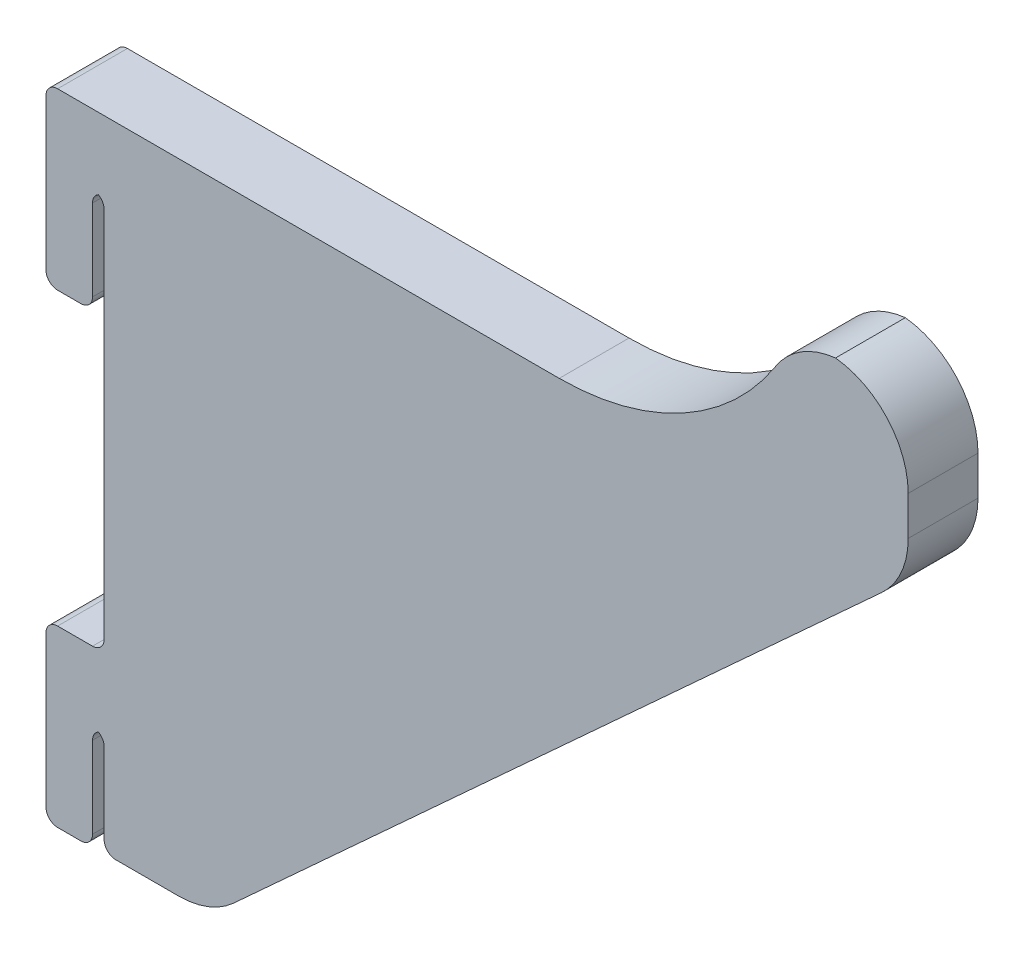
SolidWorks part; units mm, degrees
ref_plane "Plan de face" through (0, 0, 0) normal (0, 0, 1) x (1, 0, 0)
ref_plane "Plan de dessus" through (0, 0, 0) normal (0, 1, 0) x (1, 0, 0)
ref_plane "Plan de droite" through (0, 0, 0) normal (1, 0, 0) x (0, 0, -1)
sketch "Esquisse1" plane through (0, 0, 0) normal (0, 0, 1) x (1, 0, 0)
  line L0 (0, 0) -> (0, 9)
  line L1 (0, 9) -> (1, 9)
  line L4 (1, 0.0964) -> (10.1219, 0.0964)
  line L8 (10.1219, 55) -> (-4, 55)
  line L9 (1, 49) -> (0, 49)
  line L10 (0, 0) -> (-4, 0)
  line L11 (-4, 0) -> (-4, 15)
  line L12 (-4, 15) -> (1, 15)
  line L13 (1, 15) -> (1, 49)
  line L14 (0, 49) -> (0, 40)
  line L15 (0, 40) -> (-4, 40)
  line L16 (-4, 40) -> (-4, 55)
  line L17 (1, 9) -> (1, 0.0964)
  line L18 (10.1219, 55) -> (70.1219, 55) construction
  line L19 (10.1219, 55) -> (19.2932, 55)
  line L21 (60.4324, 68.4362) -> (70.1219, 68.4362)
  line L22 (70.1219, 68.4362) -> (70.1219, 55)
  line L23 (70.1219, 55) -> (10.1219, 0.0964)
  line L25 (40.1219, 55) -> (19.2932, 55)
  arc A1 (40.1219, 55) -> (60.4324, 68.4362) centre (40.1219, 77.0691) ccw
  point P11 (0.5, 9)
  dimension "D1" = 40
  dimension "D2" = 1
  dimension "D3" = 1
  dimension "D4" = 15
  dimension "D5" = 15
  dimension "D6" = 4
  dimension "D7" = 4
  dimension "D8" = 6
  dimension "D9" = 6
  dimension "D10" = 60
extrude "Boss.-Extru.1" add sketch "Esquisse1" along normal mid plane 6
fillet "Congé3" radius 1 12 edges at (1, 0.0964, 0) (1, 9, 0) (0, 9, 0) (0, 0, 0) (-4, 0, 0) (-4, 15, 0) (1, 15, 0) (0, 40, 0) (-4, 40, 0) (-4, 55, 0) (1, 49, 0) (0, 49, 0)
fillet "Congé4" radius 7 4 edges at (10.1219, 0.0964, 0) (70.1219, 55, 0) (70.1219, 68.4362, 0) (60.4324, 68.4362, 0)
